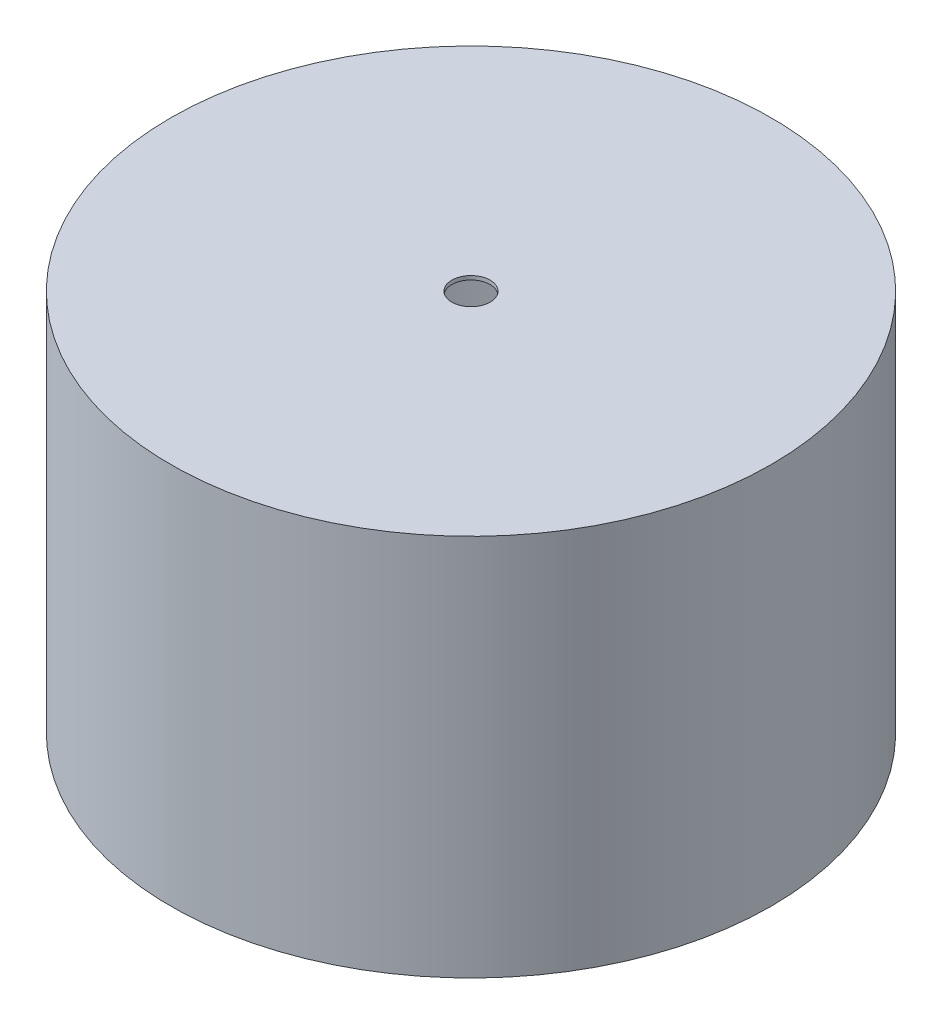
SolidWorks part; units mm, degrees
ref_plane "Front" through (0, 0, 0) normal (0, 0, 1) x (1, 0, 0)
ref_plane "Top" through (0, 0, 0) normal (0, 1, 0) x (1, 0, 0)
ref_plane "Right" through (0, 0, 0) normal (1, 0, 0) x (0, 0, -1)
sketch "Sketch1" plane through (0, 0, 0) normal (0, 1, 0) x (1, 0, 0)
  circle A0 centre (0, 0) radius 77.5
  dimension "D1" = 155
extrude "Boss-Extrude1" add sketch "Sketch1" against normal blind 1
extrude "Extrude-Thin1" add sketch "Sketch1<2>" against normal blind 100 thin thin type one direction wall 1
sketch "Sketch1<2>" plane through (0, 0, 0) normal (0, 1, 0) x (1, 0, 0) same geometry as "Sketch1"
sketch "Sketch2" plane through (0, 0, 0) normal (0, 1, 0) x (1, 0, 0)
  circle A0 centre (0, 0) radius 5
  dimension "D1" = 10
extrude "Cut-Extrude1" cut sketch "Sketch2" against normal through all
equation "\"Kova_d\"= 155mm"
equation "\"Kova_h\"= 100mm"
equation "\"D1@Sketch1\"=\"Kova_d\""
equation "\"D1@Extrude-Thin1\"=\"Kova_h\""
